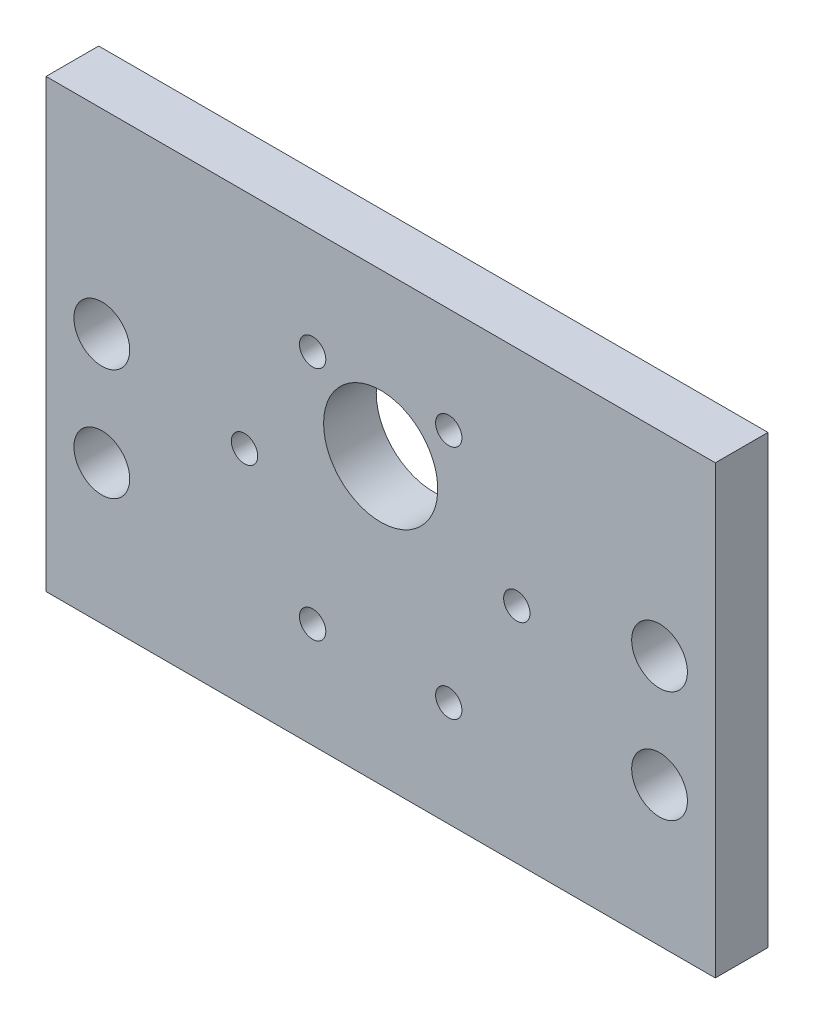
SolidWorks part; units mm, degrees
ref_plane "Front Plane" through (0, 0, 0) normal (0, 0, 1) x (1, 0, 0)
ref_plane "Top Plane" through (0, 0, 0) normal (0, 1, 0) x (1, 0, 0)
ref_plane "Right Plane" through (0, 0, 0) normal (1, 0, 0) x (0, 0, -1)
sketch "Sketch1" plane through (0, 0, 0) normal (0, 0, 1) x (1, 0, 0)
  line L0 (38.1, 50.8) -> (38.1, 0) construction
  line L1 (0, 0) -> (76.2, 0)
  line L2 (0, 0) -> (0, 50.8)
  line L3 (0, 50.8) -> (76.2, 50.8)
  line L4 (76.2, 0) -> (76.2, 50.8)
  line L5 (-6.35, 25.4) -> (82.55, 25.4) construction
  line L6 (38.1, 25.4) -> (70.1013, 80.8279) construction
  line L7 (38.1, 25.4) -> (75.3916, -39.1909) construction
  circle A0 centre (38.1, 32.4) radius 6.5
  circle A1 centre (38.1, 25.4) radius 18.5 construction
  circle A2 centre (22.6, 25.4) radius 1.5
  circle A3 centre (53.6, 25.4) radius 1.5
  circle A4 centre (45.85, 11.9766) radius 1.5
  circle A5 centre (30.35, 11.9766) radius 1.5
  circle A6 centre (30.35, 38.8234) radius 1.5
  circle A7 centre (45.85, 38.8234) radius 1.5
  circle A8 centre (38.1, 25.4) radius 15.5 construction
  circle A9 centre (6.35, 28.575) radius 3.175
  circle A10 centre (6.35, 15.875) radius 3.175
  circle A11 centre (69.85, 28.575) radius 3.175
  circle A12 centre (69.85, 15.875) radius 3.175
  dimension "D3" = 13
  dimension "D4" = 37
  dimension "D7" = 3
  dimension "D10" = 31
  dimension "D12" = 15.875
  dimension "D15" = 6.35
  dimension "D1" = 76.2
  dimension "D2" = 50.8
  dimension "D5" = 7
  dimension "D6" = 25.4
  dimension "D8" = 60
  dimension "D9" = 60
  dimension "D11" = 12.7
  dimension "D13" = 6.35
  dimension "D14" = 6.35
extrude "Boss-Extrude1" add sketch "Sketch1" along normal blind 5.9944
